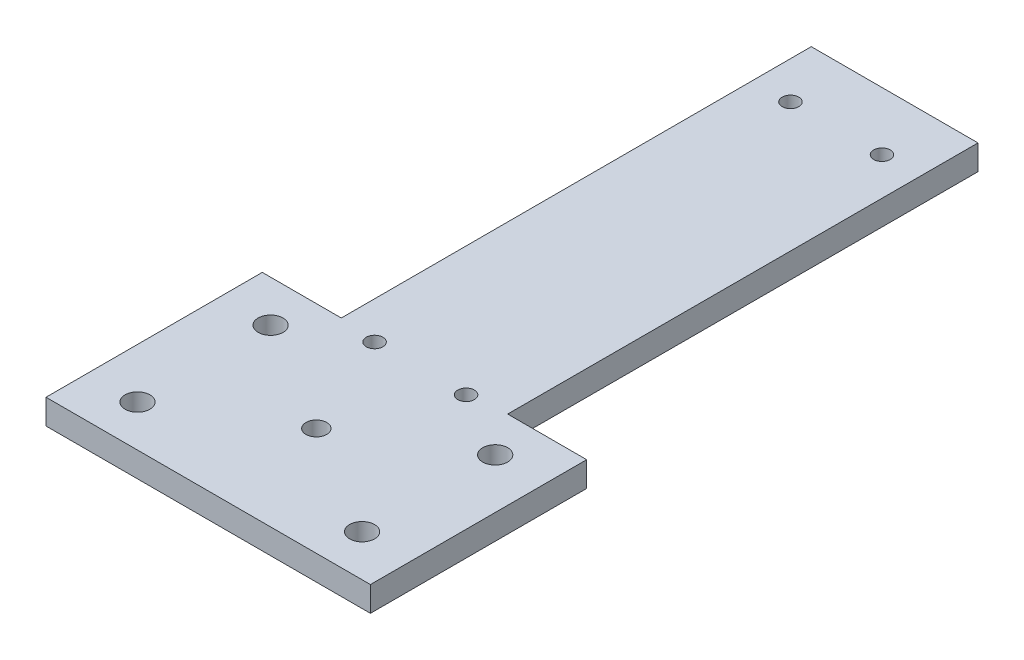
SolidWorks part; units mm, degrees
ref_plane "Front Plane" through (0, 0, 0) normal (1, 0, 0) x (0, 1, 0)
ref_plane "Top Plane" through (0, 0, 0) normal (0, 0, 1) x (0, 1, 0)
ref_plane "Right Plane" through (0, 0, 0) normal (0, 1, 0) x (-1, 0, 0)
sketch "Sketch2" plane through (0, 1180.4362, 0) normal (0, 1, 0) x (1, 0, 0)
  line L0 (845.275, -1925.9111) -> (831.275, -1925.9111) construction
  line L8 (791.275, -1925.9111) -> (777.275, -1925.9111) construction
  line L16 (845.275, -1925.9111) -> (831.275, -1925.9111)
  line L24 (791.275, -1925.9111) -> (777.275, -1925.9111)
  line L32 (791.275, -1807.9111) -> (791.275, -1920.9111)
  line L33 (772.275, -1920.9111) -> (791.275, -1920.9111)
  line L34 (772.275, -1920.9111) -> (772.275, -1972.9111)
  line L35 (772.275, -1972.9111) -> (850.275, -1972.9111)
  line L36 (850.275, -1920.911) -> (850.275, -1972.9111)
  line L37 (831.275, -1920.911) -> (831.3604, -1807.9111)
  line L38 (791.275, -1807.9111) -> (831.3604, -1807.9111)
  line L39 (831.275, -1920.911) -> (850.275, -1920.911)
  line L40 (796.275, -1936.9111) -> (796.275, -1806.9111) construction
  line L43 (777.275, -1967.9111) -> (777.275, -1925.9111) construction
  line L44 (845.275, -1967.9111) -> (831.275, -1967.9111) construction
  line L45 (845.275, -1925.9111) -> (845.275, -1967.9111) construction
  circle A0 centre (811.275, -1946.9111) radius 2.5
  circle A1 centre (784.275, -1930.9111) radius 3
  circle A2 centre (784.275, -1930.9111) radius 3
  circle A3 centre (784.275, -1962.9111) radius 3
  circle A4 centre (784.275, -1962.9111) radius 3
  circle A5 centre (838.275, -1930.9111) radius 3
  circle A6 centre (838.275, -1930.9111) radius 3
  circle A7 centre (838.275, -1962.9111) radius 3
  circle A8 centre (838.275, -1962.9111) radius 3
  circle A9 centre (800.275, -1921.9111) radius 2
  circle A10 centre (800.275, -1921.9111) radius 2
  circle A11 centre (800.275, -1821.9111) radius 2
  circle A12 centre (800.275, -1821.9111) radius 2
  circle A13 centre (822.275, -1921.9111) radius 2
  circle A14 centre (822.275, -1921.9111) radius 2
  circle A15 centre (822.275, -1821.9111) radius 2
  circle A16 centre (822.275, -1821.9111) radius 2
  dimension "D16" = 5
  dimension "D9" = 5
  dimension "D10" = 165
  dimension "D11" = 5
  dimension "D12" = 5
  dimension "D13" = 5
  dimension "D14" = 40
  dimension "D15" = 5
  dimension "D17" = 39
  dimension "D18" = 26
  dimension "D19" = 0.043
  dimension "D1" = 0
  dimension "D2" = 0
  dimension "D3" = 0
  dimension "D4" = 0
  dimension "D5" = 0
  dimension "D6" = 0
  dimension "D7" = 0
  dimension "D8" = 0
extrude "Boss-Extrude1" add sketch "Sketch2" along normal blind 6 contours L39 L37 L38 L32 L33 L34 L35 L36 A16 A14 A8 A6 A4 A2 region at (811.2865, 1180.4362, 1902.8974)
